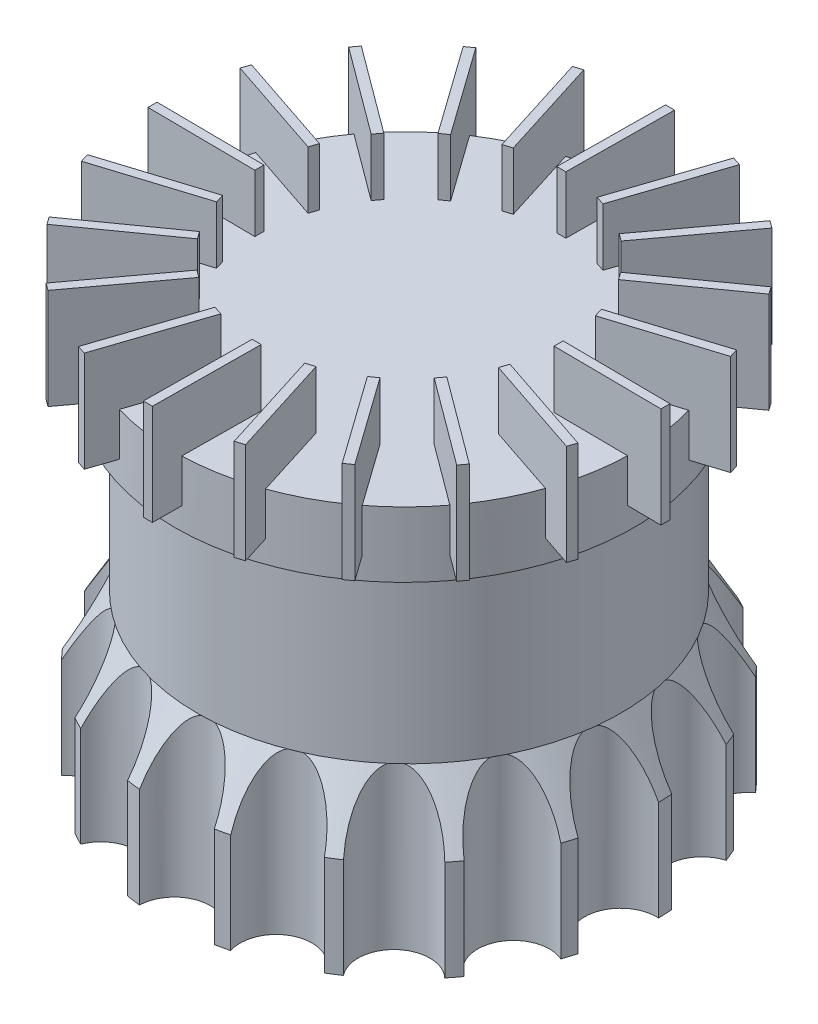
SolidWorks part; units mm, degrees
ref_plane "Front Plane" through (0, 0, 0) normal (0, 0, 1) x (1, 0, 0)
ref_plane "Top Plane" through (0, 0, 0) normal (0, 1, 0) x (1, 0, 0)
ref_plane "Right Plane" through (0, 0, 0) normal (1, 0, 0) x (0, 0, -1)
sketch "Sketch1" plane through (0, 0, 0) normal (0, 1, 0) x (1, 0, 0)
  circle A0 centre (0, 0) radius 43.4022
  dimension "D1" = 86.8045
extrude "Boss-Extrude1" add sketch "Sketch1" along normal blind 28.702
sketch "Sketch2" plane through (0, 28.702, 0) normal (0, 1, 0) x (1, 0, 0)
  circle A0 centre (-36.5967, -23.3331) radius 6.35
  circle A1 centre (0, 0) radius 43.4022 construction
  circle A2 centre (-42.3701, -9.4091) radius 6.35
  circle A3 centre (-43.033, 5.6497) radius 6.35
  circle A4 centre (-38.5054, 20.0271) radius 6.35
  circle A5 centre (-29.3336, 31.989) radius 6.35
  circle A6 centre (-16.6237, 40.0925) radius 6.35
  circle A7 centre (-1.9087, 43.3603) radius 6.35
  circle A8 centre (13.0365, 41.3981) radius 6.35
  circle A9 centre (26.4093, 34.4428) radius 6.35
  circle A10 centre (36.5967, 23.3331) radius 6.35
  circle A11 centre (42.3701, 9.4091) radius 6.35
  circle A12 centre (43.033, -5.6497) radius 6.35
  circle A13 centre (38.5054, -20.0271) radius 6.35
  circle A14 centre (29.3336, -31.989) radius 6.35
  circle A15 centre (16.6237, -40.0925) radius 6.35
  circle A16 centre (1.9087, -43.3603) radius 6.35
  circle A17 centre (-13.0365, -41.3981) radius 6.35
  circle A18 centre (-26.4093, -34.4428) radius 6.35
  point P40 (0, 0)
  dimension "D1" = 18
extrude "Cut-Extrude1" cut sketch "Sketch2" against normal blind 80.8736
sketch "Sketch3" plane through (0, 28.702, 0) normal (0, 1, 0) x (1, 0, 0)
  circle A0 centre (0, 0) radius 37.0523
  arc A1 (-41.0156, 14.1943) -> (-35.1711, 25.4313) centre (-38.5054, 20.0271) ccw construction
extrude "Cut-Extrude2" cut sketch "Sketch3" against normal blind 80.8736 draft 30 flip side to cut
sketch "Sketch4" plane through (0, 28.702, 0) normal (0, 1, 0) x (1, 0, 0)
  circle A0 centre (0, 0) radius 37.4269
  dimension "D1" = 74.8538
extrude "Boss-Extrude2" add sketch "Sketch4" along normal blind 29.5961
sketch "Sketch5" plane through (0, 58.2981, 0) normal (0, 1, 0) x (1, 0, 0)
  circle A0 centre (-0.8, 0) radius 40.5971
  circle A1 centre (0, 0) radius 37.4269 construction
  dimension "D1" = 0.8
extrude "Boss-Extrude3" add sketch "Sketch5" along normal blind 11.5443
sketch "Sketch7" plane through (0, 69.8424, 0) normal (0, 1, 0) x (1, 0, 0)
  line L0 (0, 0) -> (-27.2044, -36.7456) construction
  line L1 (-16.5122, -20.9589) -> (-27.8474, -36.2695)
  line L2 (-15.2263, -21.9109) -> (-26.5615, -37.2216)
  line L3 (-27.8474, -36.2695) -> (-26.5615, -37.2216)
  line L4 (-0.643, 0.476) -> (-32.0437, -41.9376) construction
  line L5 (0, 0) -> (-31.4007, -42.4136) construction
  line L6 (0.643, -0.476) -> (-30.7578, -42.8896) construction
  line L7 (-16.5122, -20.9589) -> (-15.2263, -21.9109)
  line L8 (-21.2519, -16.1334) -> (-36.7636, -27.1919)
  line L9 (-37.6924, -25.8891) -> (-36.7636, -27.1919)
  line L10 (-22.1807, -14.8305) -> (-37.6924, -25.8891)
  line L11 (-22.1807, -14.8305) -> (-21.2519, -16.1334)
  line L12 (-25.1973, -8.7765) -> (-43.367, -14.5005)
  line L13 (-43.8477, -12.9744) -> (-43.367, -14.5005)
  line L14 (-25.678, -7.2505) -> (-43.8477, -12.9744)
  line L15 (-25.678, -7.2505) -> (-25.1973, -8.7765)
  line L16 (-26.6761, -0.5606) -> (-45.7253, -0.3896)
  line L17 (-45.711, 1.2103) -> (-45.7253, -0.3896)
  line L18 (-26.6617, 1.0393) -> (-45.711, 1.2103)
  line L19 (-26.6617, 1.0393) -> (-26.6761, -0.5606)
  line L20 (-25.5437, 7.7102) -> (-43.6078, 13.7594)
  line L21 (-43.0997, 15.2766) -> (-43.6078, 13.7594)
  line L22 (-25.0357, 9.2274) -> (-43.0997, 15.2766)
  line L23 (-25.0357, 9.2274) -> (-25.5437, 7.7102)
  line L24 (-21.9109, 15.2263) -> (-37.2216, 26.5615)
  line L25 (-36.2695, 27.8474) -> (-37.2216, 26.5615)
  line L26 (-20.9589, 16.5122) -> (-36.2695, 27.8474)
  line L27 (-20.9589, 16.5122) -> (-21.9109, 15.2263)
  line L28 (-16.1334, 21.2519) -> (-27.1919, 36.7636)
  line L29 (-25.8891, 37.6924) -> (-27.1919, 36.7636)
  line L30 (-14.8305, 22.1807) -> (-25.8891, 37.6924)
  line L31 (-14.8305, 22.1807) -> (-16.1334, 21.2519)
  line L32 (-8.7765, 25.1973) -> (-14.5005, 43.367)
  line L33 (-12.9744, 43.8477) -> (-14.5005, 43.367)
  line L34 (-7.2505, 25.678) -> (-12.9744, 43.8477)
  line L35 (-7.2505, 25.678) -> (-8.7765, 25.1973)
  line L36 (-0.5606, 26.6761) -> (-0.3896, 45.7253)
  line L37 (1.2103, 45.711) -> (-0.3896, 45.7253)
  line L38 (1.0393, 26.6617) -> (1.2103, 45.711)
  line L39 (1.0393, 26.6617) -> (-0.5606, 26.6761)
  line L40 (7.7102, 25.5437) -> (13.7594, 43.6078)
  line L41 (15.2766, 43.0997) -> (13.7594, 43.6078)
  line L42 (9.2274, 25.0357) -> (15.2766, 43.0997)
  line L43 (9.2274, 25.0357) -> (7.7102, 25.5437)
  line L44 (15.2263, 21.9109) -> (26.5615, 37.2216)
  line L45 (27.8474, 36.2695) -> (26.5615, 37.2216)
  line L46 (16.5122, 20.9589) -> (27.8474, 36.2695)
  line L47 (16.5122, 20.9589) -> (15.2263, 21.9109)
  line L48 (21.2519, 16.1334) -> (36.7636, 27.1919)
  line L49 (37.6924, 25.8891) -> (36.7636, 27.1919)
  line L50 (22.1807, 14.8305) -> (37.6924, 25.8891)
  line L51 (22.1807, 14.8305) -> (21.2519, 16.1334)
  line L52 (25.1973, 8.7765) -> (43.367, 14.5005)
  line L53 (43.8477, 12.9744) -> (43.367, 14.5005)
  line L54 (25.678, 7.2505) -> (43.8477, 12.9744)
  line L55 (25.678, 7.2505) -> (25.1973, 8.7765)
  line L56 (26.6761, 0.5606) -> (45.7253, 0.3896)
  line L57 (45.711, -1.2103) -> (45.7253, 0.3896)
  line L58 (26.6617, -1.0393) -> (45.711, -1.2103)
  line L59 (26.6617, -1.0393) -> (26.6761, 0.5606)
  line L60 (25.5437, -7.7102) -> (43.6078, -13.7594)
  line L61 (43.0997, -15.2766) -> (43.6078, -13.7594)
  line L62 (25.0357, -9.2274) -> (43.0997, -15.2766)
  line L63 (25.0357, -9.2274) -> (25.5437, -7.7102)
  line L64 (21.9109, -15.2263) -> (37.2216, -26.5615)
  line L65 (36.2695, -27.8474) -> (37.2216, -26.5615)
  line L66 (20.9589, -16.5122) -> (36.2695, -27.8474)
  line L67 (20.9589, -16.5122) -> (21.9109, -15.2263)
  line L68 (16.1334, -21.2519) -> (27.1919, -36.7636)
  line L69 (25.8891, -37.6924) -> (27.1919, -36.7636)
  line L70 (14.8305, -22.1807) -> (25.8891, -37.6924)
  line L71 (14.8305, -22.1807) -> (16.1334, -21.2519)
  line L72 (8.7765, -25.1973) -> (14.5005, -43.367)
  line L73 (12.9744, -43.8477) -> (14.5005, -43.367)
  line L74 (7.2505, -25.678) -> (12.9744, -43.8477)
  line L75 (7.2505, -25.678) -> (8.7765, -25.1973)
  line L76 (0.5606, -26.6761) -> (0.3896, -45.7253)
  line L77 (-1.2103, -45.711) -> (0.3896, -45.7253)
  line L78 (-1.0393, -26.6617) -> (-1.2103, -45.711)
  line L79 (-1.0393, -26.6617) -> (0.5606, -26.6761)
  line L80 (-7.7102, -25.5437) -> (-13.7594, -43.6078)
  line L81 (-15.2766, -43.0997) -> (-13.7594, -43.6078)
  line L82 (-9.2274, -25.0357) -> (-15.2766, -43.0997)
  line L83 (-9.2274, -25.0357) -> (-7.7102, -25.5437)
  point P90 (0, 0)
  dimension "D1" = 0.8
  dimension "D3" = 45.72
  dimension "D4" = 19.05
  dimension "D2" = 0.8
  dimension "D5" = 20
extrude "Boss-Extrude4" add sketch "Sketch7" along normal blind 10.16 and the other way blind 7.62
scale "Scale1" scale about centroid uniform scaling yes scale factor 0.06
